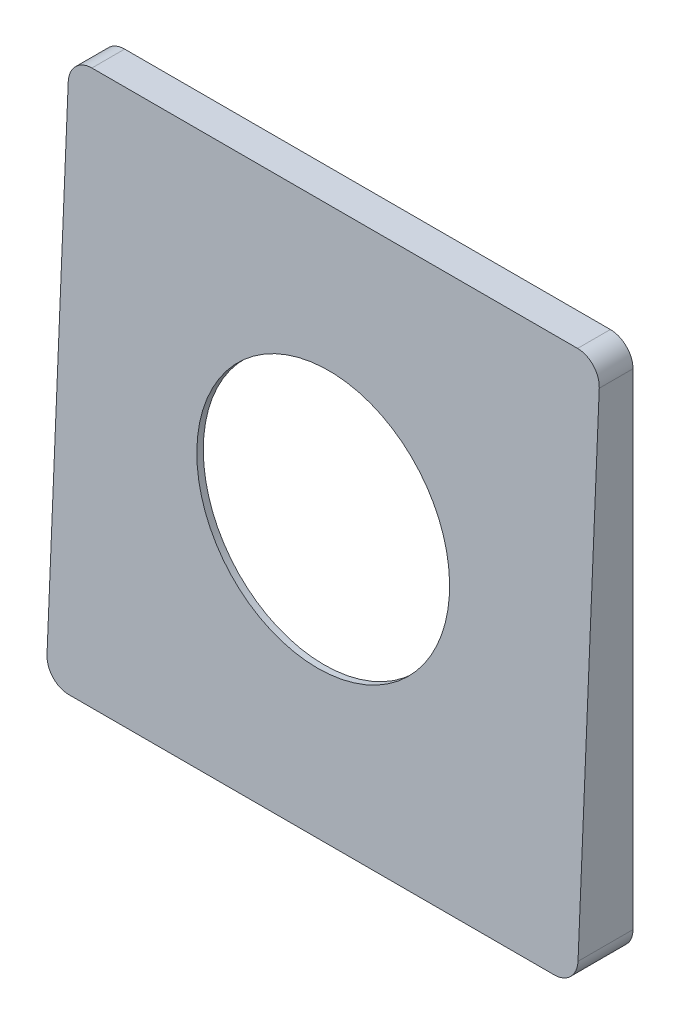
SolidWorks part; units mm, degrees
ref_plane "Front Plane" through (0, 0, 0) normal (0, 0, 1) x (1, 0, 0)
ref_plane "Top Plane" through (0, 0, 0) normal (0, 1, 0) x (1, 0, 0)
ref_plane "Right Plane" through (0, 0, 0) normal (1, 0, 0) x (0, 0, -1)
sketch "Sketch1" plane through (0, 0, 0) normal (0, 0, 1) x (1, 0, 0)
  line L0 (-38.566, 0) -> (72.4153, 0) construction
  line L1 (0, -49.5581) -> (0, 74.5126) construction
  line L2 (-37.5, 40) -> (37.5, 40)
  line L3 (-40, 37.5) -> (-40, -37.5)
  line L4 (-37.5, -40) -> (37.5, -40)
  line L5 (40, 37.5) -> (40, -37.5)
  arc A0 (-40, -37.5) -> (-37.5, -40) centre (-37.5, -37.5) ccw
  arc A1 (37.5, -40) -> (40, -37.5) centre (37.5, -37.5) ccw
  arc A2 (37.5, 40) -> (40, 37.5) centre (37.5, 37.5) cw
  arc A3 (-37.5, 40) -> (-40, 37.5) centre (-37.5, 37.5) ccw
  dimension "D3" = 2.5
  dimension "D1" = 80
  dimension "D2" = 80
  dimension "D4" = 40
  dimension "D5" = 40
extrude "Extrude-Thin1" add sketch "Sketch1" along normal blind 8 thin thin type one direction wall 1
sketch "Sketch5" plane through (41, 0, 0) normal (1, 0, 0) x (0, 0, -1)
  line L0 (20.3178, 0) -> (-25.0092, 0) construction
  line L1 (0, 43.59) -> (0, -45.2443) construction
  line L2 (-3.4562, 41) -> (-8, 41)
  line L3 (-8, 41) -> (-8, -41)
  line L4 (-8, -41) -> (-7.0437, -41)
  line L6 (-7.0437, -41) -> (-3.4562, 41)
  line L7 (-8, -41) -> (0, -41) construction
  line L11 (-8, 41) -> (0, 41) construction
extrude "Cut-Extrude2" cut sketch "Sketch5" against normal blind 120
sketch "Sketch6" plane through (41, 0, 0) normal (1, 0, 0) x (0, 0, -1)
  line L0 (-7.0437, -41) -> (-3.4562, 41)
  line L1 (-3.4562, 41) -> (-4.4572, 41)
  line L2 (-4.4572, 41) -> (-8.0447, -41)
  line L3 (-8.0447, -41) -> (-7.0437, -41)
  line L4 (-3.4562, 41) -> (-3.4562, 45.0301) construction
  dimension "D1" = 1
  dimension "D2" = 90
extrude "Boss-Extrude1" add sketch "Sketch6" against normal blind 82
sketch "Sketch7" plane through (0, 0, 0) normal (0, 0, -1) x (-1, 0, 0)
  line L0 (0, 0) -> (0, 69.537) construction
  line L1 (71.0569, 0) -> (20.5255, 0) construction
  line L2 (-37.5, 41) -> (37.5, 41)
  line L3 (-37.5, 41) -> (37.5, 41) construction
  line L4 (-41, -37.5) -> (-41, 37.5)
  line L5 (41, -37.5) -> (41, 37.5)
  line L6 (-41, -37.5) -> (-41, 37.5) construction
  line L7 (-37.5, -41) -> (37.5, -41)
  arc A0 (37.5, 41) -> (41, 37.5) centre (37.5, 37.5) cw
  arc A1 (-37.5, -41) -> (-41, -37.5) centre (-37.5, -37.5) cw
  arc A2 (37.5, -41) -> (41, -37.5) centre (37.5, -37.5) ccw
  arc A4 (-37.5, 41) -> (-41, 37.5) centre (-37.5, 37.5) ccw
  point P9 (0, -41)
  point P13 (-41, 0)
  point P14 (0, 41)
  point P25 (41, 0)
extrude "Cut-Extrude-Thin1" cut sketch "Sketch7" against normal blind 82 thin thin type one direction wall 11
sketch "Sketch8" plane through (0, 0.273, 6.239) normal (0, 0.0437, 0.999) x (1, 0, 0)
  line L0 (0, 0) -> (0, 28.9526) construction
  line L1 (23.1598, 0) -> (-27.4609, 0) construction
  circle A0 centre (0, 0) radius 19.5
  dimension "D1" = 39
extrude "Cut-Extrude3" cut sketch "Sketch8" against normal blind 82
sketch "Sketch10" plane through (0, 0, 0) normal (0, 0, -1) x (-1, 0, 0)
  line L0 (0, 0) -> (0, 31.0175) construction
  line L1 (27.13, 0) -> (-25.8066, 0) construction
  line L2 (-37.5, 40) -> (37.5, 40)
  line L3 (-40, 37.5) -> (-40, -37.5)
  line L4 (-37.5, -40) -> (37.5, -40)
  line L5 (40, 37.5) -> (40, -37.5)
  arc A0 (-40, -37.5) -> (-37.5, -40) centre (-37.5, -37.5) ccw
  arc A1 (37.5, -40) -> (40, -37.5) centre (37.5, -37.5) ccw
  arc A2 (37.5, 40) -> (40, 37.5) centre (37.5, 37.5) cw
  arc A3 (-37.5, 40) -> (-40, 37.5) centre (-37.5, 37.5) ccw
  dimension "D3" = 2.5
  dimension "D1" = 80
  dimension "D2" = 80
  dimension "D4" = 40
  dimension "D5" = 40
extrude "Extrude-Thin2" add sketch "Sketch10" along normal blind 0.6 thin thin type one direction wall 1
